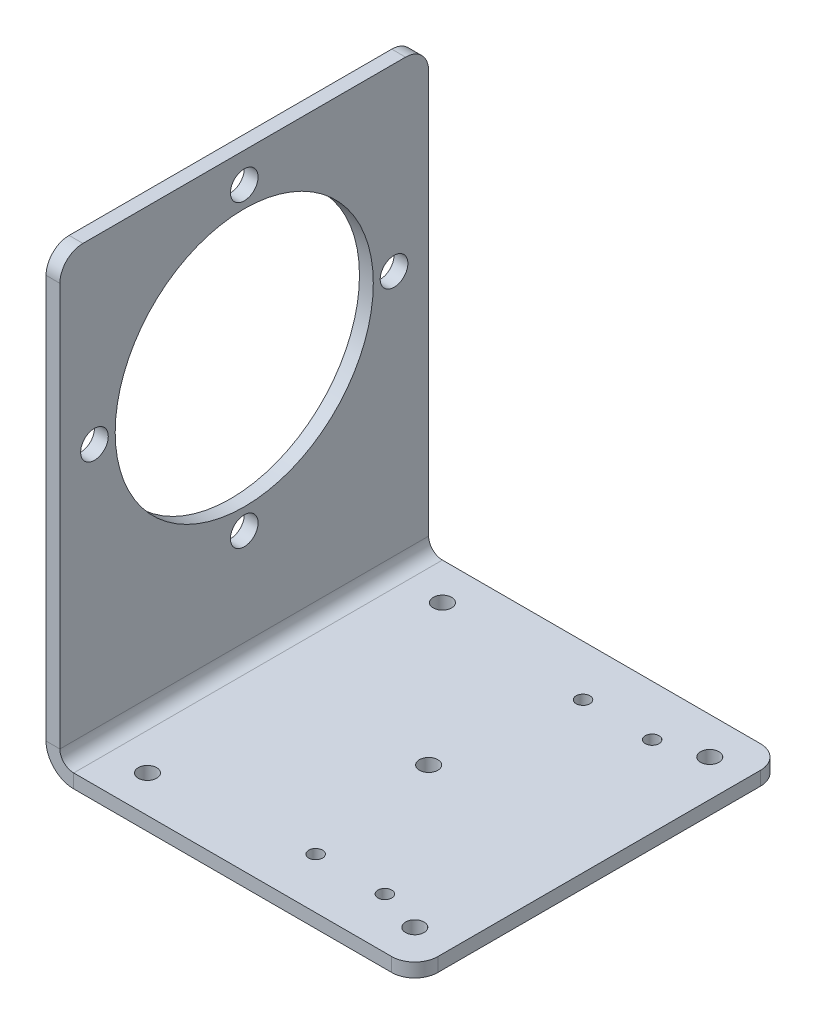
SolidWorks part; units mm, degrees
note: The reader was unsure of these and kept them because the rebuilt part matched: flange length of "邊線-凸緣1".
material "1060 Alloy"
ref_plane "Front Plane" through (0, 0, 0) normal (0, 0, 1) x (1, 0, 0)
ref_plane "Top Plane" through (0, 0, 0) normal (0, 1, 0) x (1, 0, 0)
ref_plane "Right Plane" through (0, 0, 0) normal (1, 0, 0) x (0, 0, -1)
sketch "Sketch1" plane through (0, 0, 0) normal (1, 0, 0) x (0, 0, -1)
  line L0 (0, 59.5) -> (80, 59.5) construction
  line L1 (0, 0) -> (80, 0)
  line L2 (0, 0) -> (0, 98.5)
  line L3 (0, 98.5) -> (80, 98.5)
  line L4 (80, 0) -> (80, 98.5)
  circle A0 centre (40, 59.5) radius 28
  dimension "D1" = 56
  dimension "D2" = 39
  dimension "D3" = 80
  dimension "D4" = 98.5
base flange "Base-Flange1" sketch "Sketch1" thickness 3 reverse thickness direction no parameters "D1"=3
hole_wizard "Ø6.0 (6) Diameter Hole1" positions "Sketch2" profile "Sketch3" hole size "Ø6.0" standard "ISO" end condition through all
sketch "Sketch2" plane through (0, 0, 0) normal (1, 0, 0) x (0, 0, -1)
  circle A0 centre (40, 59.5) radius 32.5 construction
  point P4 (40, 92)
  dimension "D1" = 65
sketch "Sketch3" plane through (0, 92, -40) normal (0, 1, 0) x (0, 0, -1)
  line L0 (0, 0) -> (0, 3)
  line L1 (0, 3) -> (3, 3)
  line L2 (3, 3) -> (3, 0)
  line L5 (3, 0) -> (0, 0)
  line L11 (0, -6.35) -> (0, 107.95) construction
  dimension "Thru Hole Dia." = 6
  dimension "Thru Hole Depth" = 3
pattern_circular "CirPattern1" count 4 over 360 about axis through (0, 59.5, -40) along (1, 0, 0) of "Ø6.0 (6) Diameter Hole1"
edge flange "邊線-凸緣1" sketch "Sketch6" flange angle 90 flange length 80 flange position material inside bend radius 3 thickness 3 relief rectangular parameters "D6"=10
sketch "Sketch6" plane through (0, 0, 0) normal (0, -1, 0) x (0, 0, -1)
  line L2 (0, 0) -> (0, 77)
  line L3 (0, 77) -> (80, 77)
  line L4 (80, 77) -> (80, 0)
  line L7 (0, 0) -> (80, 0) construction
  line L8 (0, 0) -> (80, 0)
bend "邊線彎折1" bend radius 3 bend angle 90 parameters "D5"=1
fillet "Fillet1" radius 5 4 edges at (77, 1.5, 0) (77, 1.5, -80) (-1.5, 98.5, -80) (-1.5, 98.5, 0)
sketch "Sketch25" plane through (0, 3, 0) normal (0, 1, 0) x (1, 0, 0)
  line L0 (69, 0) -> (69, 8) construction
  line L1 (72, 0) -> (3, 0) construction
  line L2 (3, 80) -> (72, 80) construction
  line L3 (77, 75) -> (77, 5) construction
  line L4 (77, 8) -> (69, 8) construction
  line L5 (69, 8) -> (11, 8) construction
  line L6 (11, 8) -> (3, 8) construction
  line L7 (3, 0) -> (3, 80) construction
  line L8 (11, 8) -> (11, 72) construction
  line L9 (11, 72) -> (69, 72) construction
  line L10 (69, 72) -> (77, 72) construction
  line L11 (69, 72) -> (69, 80) construction
  line L12 (69, 8) -> (69, 72) construction
  line L13 (11, 8) -> (69, 72) construction
  dimension "D2" = 8
  dimension "D3" = 8
hole_wizard "Ø4.0 (4) Diameter Hole4" positions "Sketch26" profile "Sketch27" hole size "Ø4.0" standard "ISO" end condition through all
sketch "Sketch26" plane through (0, 3, 0) normal (0, 1, 0) x (1, 0, 0)
  line L0 (11, 8) -> (69, 72) construction
  point P0 (11, 8)
  point P3 (11, 72)
  point P6 (69, 72)
  point P9 (69, 8)
  point P13 (40, 40)
sketch "Sketch27" plane through (11, 3, -8) normal (1, 0, 0) x (0, 0, 1)
  line L0 (0, 0) -> (0, 3)
  line L1 (0, 3) -> (2, 3)
  line L2 (2, 3) -> (2, 0)
  line L5 (2, 0) -> (0, 0)
  line L11 (0, -6.35) -> (0, 107.95) construction
  dimension "Thru Hole Dia." = 4
  dimension "Thru Hole Depth" = 3
sketch "Sketch29" plane through (0, 3, 0) normal (0, 1, 0) x (1, 0, 0)
  line L0 (52, 11) -> (52, 0) construction
  line L4 (52, 11) -> (44.5, 11) construction
  line L6 (52, 11) -> (59.5, 11) construction
  line L7 (72, 0) -> (3, 0) construction
  line L8 (77, 75) -> (77, 5) construction
  dimension "D1" = 25
  dimension "D2" = 15
  dimension "D3" = 11
hole_wizard "Ø3.0 (3) Diameter Hole2" positions "Sketch30" profile "Sketch31" hole size "Ø3.0" standard "ISO" end condition through all
sketch "Sketch30" plane through (0, 3, 0) normal (0, 1, 0) x (1, 0, 0)
  point P0 (44.5, 11)
  point P3 (59.5, 11)
sketch "Sketch31" plane through (44.5, 3, -11) normal (1, 0, 0) x (0, 0, 1)
  line L0 (0, 0) -> (0, 3)
  line L1 (0, 3) -> (1.5, 3)
  line L2 (1.5, 3) -> (1.5, 0)
  line L5 (1.5, 0) -> (0, 0)
  line L11 (0, -6.35) -> (0, 107.95) construction
  dimension "Thru Hole Dia." = 3
  dimension "Thru Hole Depth" = 3
ref_plane "Plane1" through (0, 0, -40) normal (0, 0, 1) x (1, 0, 0)
mirror "Mirror1" about plane through (0, 0, -40) normal (0, 0, 1) of "Ø3.0 (3) Diameter Hole2"
sketch "彎折-線1" [suppressed] plane through (0, 0, 0) normal (0, 1, 0) x (1, 0, 0)
sketch "邊界方塊1" [suppressed] plane through (0, 0, 0) normal (0, 1, 0) x (1, 0, 0)
sheet metal parameters "鈑金1" thickness 3 parameters "D1"=3
flat pattern "平板-型式1" [suppressed]
sketch "彎折-線2" plane through (0, 0, 0) normal (0, 1, 0) x (1, 0, 0)
sketch3d "邊界方塊2" [suppressed]
  line L0 (100, 0, 0) -> (0, 0, 0) construction
  line L1 (100, 100, 0) -> (0, 100, 0) construction
  line L2 (100, 0, 0) -> (100, 100, 0) construction
  line L3 (0, 0, 0) -> (0, 100, 0) construction
sheet metal parameters "鈑金2" thickness 3 parameters "D1"=3
flat pattern "平板-型式1"
sketch "彎折-線2" plane through (0, 0, 0) normal (0, 1, 0) x (1, 0, 0)
sketch3d "邊界方塊2" [suppressed]
  line L0 (100, 0, 0) -> (0, 0, 0) construction
  line L1 (100, 100, 0) -> (0, 100, 0) construction
  line L2 (100, 0, 0) -> (100, 100, 0) construction
  line L3 (0, 0, 0) -> (0, 100, 0) construction
sheet metal parameters "鈑金3" thickness 3 parameters "D1"=3
flat pattern "平板-型式1"
sketch "彎折-線2" plane through (0, 0, 0) normal (0, 1, 0) x (1, 0, 0)
sketch3d "邊界方塊2" [suppressed]
  line L0 (100, 0, 0) -> (0, 0, 0) construction
  line L1 (100, 98.5, 0) -> (0, 98.5, 0) construction
  line L2 (100, 0, 0) -> (100, 98.5, 0) construction
  line L3 (0, 0, 0) -> (0, 98.5, 0) construction
sheet metal parameters "鈑金4" thickness 3 parameters "D1"=3
flat pattern "平板-型式1"
sketch "彎折-線2" plane through (0, 0, 0) normal (1, 0, 0) x (0, 0, -1)
  line L0 (0, 2.6613) -> (80, 2.6613) construction
  line L1 (0, 2.6613) -> (80, 2.6613) construction
sketch3d "邊界方塊2" [suppressed]
  line L0 (0.0001, -74.6775, 0) -> (0, 98.5, 0) construction
  line L1 (80, -74.6774, 0) -> (79.9999, 98.5, 0) construction
  line L2 (0.0001, -74.6775, 0) -> (80, -74.6774, 0) construction
  line L3 (0, 98.5, 0) -> (79.9999, 98.5, 0) construction
bend of the flat pattern "平板-<邊線彎折1>1"
sheet metal parameters "鈑金10" thickness 3 parameters "D1"=3
flat pattern "平板-型式1" [suppressed]
sketch "彎折-線2" plane through (0, 0, 0) normal (1, 0, 0) x (0, 0, -1)
  line L0 (0, 2.6613) -> (80, 2.6613) construction
  line L1 (0, 2.6613) -> (80, 2.6613) construction
sketch3d "邊界方塊2" [suppressed]
  line L0 (0.0001, -74.6775, 0) -> (0, 98.5, 0) construction
  line L1 (80, -74.6774, 0) -> (79.9999, 98.5, 0) construction
  line L2 (0.0001, -74.6775, 0) -> (80, -74.6774, 0) construction
  line L3 (0, 98.5, 0) -> (79.9999, 98.5, 0) construction
bend of the flat pattern "平板-<邊線彎折1>1"
sketch "Sketch25-1" [suppressed] plane through (0, 2.3225, 0) normal (1, 0, 0) x (0, -1, 0)
  line L0 (69, 0) -> (69, 8) construction
  line L1 (72, 0) -> (-91.1775, 0) construction
  line L4 (77, 8) -> (69, 8) construction
  line L5 (69, 8) -> (11, 8) construction
  line L6 (11, 8) -> (3, 8) construction
  line L8 (11, 8) -> (11, 72) construction
  line L9 (11, 72) -> (69, 72) construction
  line L10 (69, 72) -> (77, 72) construction
  line L11 (69, 72) -> (69, 80) construction
  line L12 (69, 8) -> (69, 72) construction
  line L13 (11, 8) -> (69, 72) construction
  dimension "D2" = 8
  dimension "D3" = 8
sheet metal parameters "鈑金11" thickness 3 parameters "D1"=3
flat pattern "平板-型式1" [suppressed]
sketch "彎折-線2" plane through (0, 0, 0) normal (1, 0, 0) x (0, 0, -1)
  line L0 (0, 2.6613) -> (80, 2.6613) construction
  line L1 (0, 2.6613) -> (80, 2.6613) construction
sketch3d "邊界方塊2" [suppressed]
  line L0 (0.0001, -74.6775, 0) -> (0, 98.5, 0) construction
  line L1 (80, -74.6774, 0) -> (79.9999, 98.5, 0) construction
  line L2 (0.0001, -74.6775, 0) -> (80, -74.6774, 0) construction
  line L3 (0, 98.5, 0) -> (79.9999, 98.5, 0) construction
bend of the flat pattern "平板-<邊線彎折1>1"
sketch "Sketch25-1" plane through (0, 2.3225, 0) normal (1, 0, 0) x (0, -1, 0)
  line L0 (69, 0) -> (69, 8) construction
  line L1 (72, 0) -> (-91.1775, 0) construction
  line L4 (77, 8) -> (69, 8) construction
  line L5 (69, 8) -> (11, 8) construction
  line L6 (11, 8) -> (3, 8) construction
  line L8 (11, 8) -> (11, 72) construction
  line L9 (11, 72) -> (69, 72) construction
  line L10 (69, 72) -> (77, 72) construction
  line L11 (69, 72) -> (69, 80) construction
  line L12 (69, 8) -> (69, 72) construction
  line L13 (11, 8) -> (69, 72) construction
  dimension "D2" = 8
  dimension "D3" = 8
sketch "Sketch29-1" [suppressed] plane through (0, 2.3225, 0) normal (1, 0, 0) x (0, -1, 0)
  line L0 (52, 0) -> (52, 80) construction
  line L3 (77, 75) -> (77, 5) construction
  line L4 (52, 8) -> (44.5, 8) construction
  line L6 (52, 8) -> (59.5, 8) construction
  dimension "D1" = 25
  dimension "D2" = 15
sheet metal parameters "鈑金12" thickness 3 parameters "D1"=3
flat pattern "平板-型式1" [suppressed]
sketch "彎折-線2" plane through (0, 0, 0) normal (1, 0, 0) x (0, 0, -1)
  line L0 (0, 2.6613) -> (80, 2.6613) construction
  line L1 (0, 2.6613) -> (80, 2.6613) construction
sketch3d "邊界方塊2" [suppressed]
  line L0 (0.0001, -74.6775, 0) -> (0, 98.5, 0) construction
  line L1 (80, -74.6774, 0) -> (79.9999, 98.5, 0) construction
  line L2 (0.0001, -74.6775, 0) -> (80, -74.6774, 0) construction
  line L3 (0, 98.5, 0) -> (79.9999, 98.5, 0) construction
bend of the flat pattern "平板-<邊線彎折1>1"
sketch "Sketch25-1" plane through (0, 2.3225, 0) normal (1, 0, 0) x (0, -1, 0)
  line L0 (69, 0) -> (69, 8) construction
  line L1 (72, 0) -> (-91.1775, 0) construction
  line L4 (77, 8) -> (69, 8) construction
  line L5 (69, 8) -> (11, 8) construction
  line L6 (11, 8) -> (3, 8) construction
  line L8 (11, 8) -> (11, 72) construction
  line L9 (11, 72) -> (69, 72) construction
  line L10 (69, 72) -> (77, 72) construction
  line L11 (69, 72) -> (69, 80) construction
  line L12 (69, 8) -> (69, 72) construction
  line L13 (11, 8) -> (69, 72) construction
  dimension "D2" = 8
  dimension "D3" = 8
sketch "Sketch29-1" plane through (0, 2.3225, 0) normal (1, 0, 0) x (0, -1, 0)
  line L0 (52, 11) -> (52, 0) construction
  line L4 (52, 11) -> (44.5, 11) construction
  line L6 (52, 11) -> (59.5, 11) construction
  line L8 (77, 75) -> (77, 5) construction
  dimension "D1" = 25
  dimension "D2" = 15
  dimension "D3" = 11
